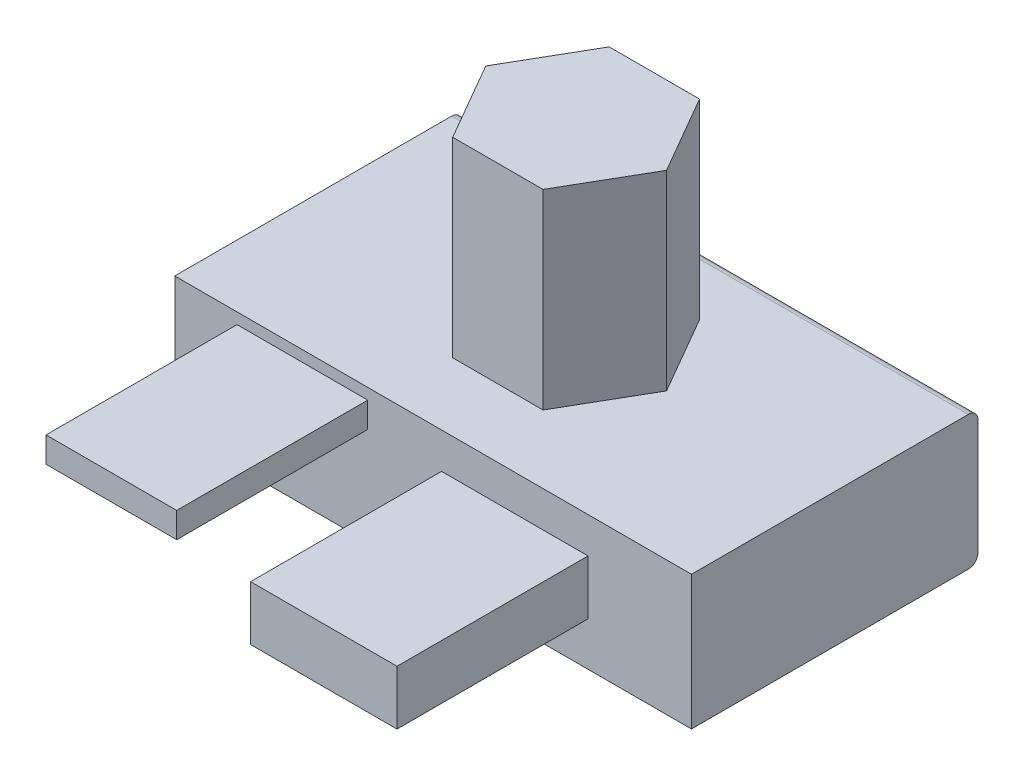
SolidWorks part; units mm, degrees
ref_plane "Front Plane" through (0, 0, 0) normal (0, 0, 1) x (1, 0, 0)
ref_plane "Top Plane" through (0, 0, 0) normal (0, 1, 0) x (1, 0, 0)
ref_plane "Right Plane" through (0, 0, 0) normal (1, 0, 0) x (0, 0, -1)
sketch "Sketch1" plane through (0, 0, 0) normal (0, 0, 1) x (1, 0, 0)
  line L1 (-68.7035, -17.821) -> (68.7035, -17.821)
  line L2 (-68.7035, -17.821) -> (-68.7035, 17.821)
  line L3 (-68.7035, 17.821) -> (68.7035, 17.821)
  line L4 (68.7035, -17.821) -> (68.7035, 17.821)
  line L5 (-68.7035, -17.821) -> (68.7035, 17.821) construction
  line L6 (-68.7035, 17.821) -> (68.7035, -17.821) construction
  point P0 (0, 0)
extrude "Boss-Extrude1" add sketch "Sketch1" along normal blind 76.2 contours L1 L4 L3 L2
sketch "Sketch2" plane through (0, 17.821, 0) normal (0, 1, 0) x (1, 0, 0)
  line L1 (23.159, -37.2907) -> (11.1437, -16.4796)
  line L2 (11.1437, -16.4796) -> (-12.8869, -16.4796)
  line L3 (-12.8869, -16.4796) -> (-24.9022, -37.2907)
  line L4 (-24.9022, -37.2907) -> (-12.8869, -58.1018)
  line L5 (-12.8869, -58.1018) -> (11.1437, -58.1018)
  line L6 (11.1437, -58.1018) -> (23.159, -37.2907)
  circle A0 centre (-0.8716, -37.2907) radius 20.8111 construction
extrude "Boss-Extrude2" add sketch "Sketch2" along normal blind 50.8
sketch "Sketch4" plane through (0, 0, 76.2) normal (0, 0, 1) x (1, 0, 0)
  line L1 (-52.1439, 14.8868) -> (-17.3813, 14.8868)
  line L2 (-52.1439, 14.8868) -> (-52.1439, 8.1274)
  line L3 (-52.1439, 8.1274) -> (-17.3813, 8.1274)
  line L4 (-17.3813, 14.8868) -> (-17.3813, 8.1274)
  line L5 (-52.1439, 14.8868) -> (-17.3813, 8.1274) construction
  line L6 (-52.1439, 8.1274) -> (-17.3813, 14.8868) construction
  line L7 (2.2531, 8.2883) -> (41.2001, 8.2883)
  line L8 (2.2531, 8.2883) -> (2.2531, -6.1961)
  line L9 (2.2531, -6.1961) -> (41.2001, -6.1961)
  line L10 (41.2001, 8.2883) -> (41.2001, -6.1961)
  line L11 (2.2531, 8.2883) -> (41.2001, -6.1961) construction
  line L12 (2.2531, -6.1961) -> (41.2001, 8.2883) construction
  point P0 (-34.7626, 11.5071)
  point P5 (21.7266, 1.0461)
extrude "Boss-Extrude4" add sketch "Sketch4" along normal blind 50.8
fillet "Fillet2" radius 2.54 2 edges at (0, -17.821, 0) (0, 17.821, 0)
